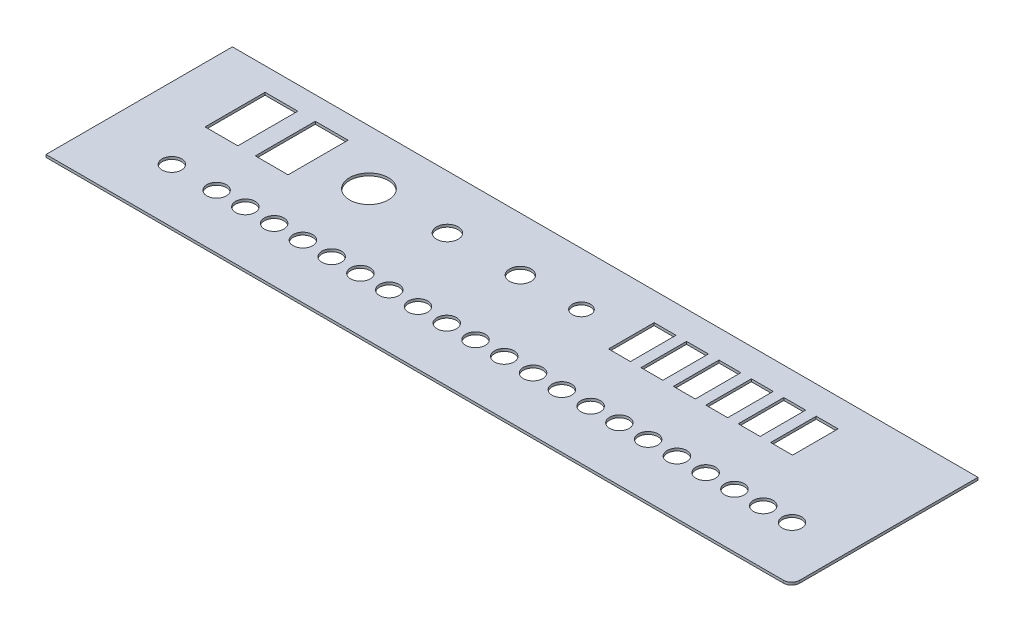
SolidWorks part; units mm, degrees
ref_plane "Front Plane" through (0, 0, 0) normal (0, 0, 1) x (1, 0, 0)
ref_plane "Top Plane" through (0, 0, 0) normal (0, 1, 0) x (1, 0, 0)
ref_plane "Right Plane" through (0, 0, 0) normal (1, 0, 0) x (0, 0, -1)
sketch "Boceto" plane through (0, 0, 0) normal (0, 1, 0) x (1, 0, 0)
  line L0 (-59.1, 30.6902) -> (-173.0029, 30.6902) construction
  line L5 (-59.1, -51.6098) -> (395.9, -51.6098) construction
  line L6 (-59.1, -51.6098) -> (-59.1, 63.3902) construction
  line L7 (-59.1, 63.3902) -> (395.9, 63.3902) construction
  line L8 (395.9, -51.6098) -> (395.9, 63.3902) construction
  line L9 (-28.6, 48.9902) -> (-8.6, 48.9902) construction
  line L10 (-28.6, 48.9902) -> (-28.6, 12.3902) construction
  line L11 (-28.6, 12.3902) -> (-8.6, 12.3902) construction
  line L12 (-8.6, 48.9902) -> (-8.6, 12.3902) construction
  line L13 (-28.6, 48.9902) -> (-8.6, 12.3902) construction
  line L14 (-28.6, 12.3902) -> (-8.6, 48.9902) construction
  line L15 (-59.1, -18.1098) -> (395.9, -18.1098) construction
  line L16 (2.4, 12.3902) -> (22.4, 12.3902) construction
  line L17 (2.4, 12.3902) -> (2.4, 48.9902) construction
  line L18 (2.4, 48.9902) -> (22.4, 48.9902) construction
  line L19 (22.4, 12.3902) -> (22.4, 48.9902) construction
  line L20 (2.4, 12.3902) -> (22.4, 48.9902) construction
  line L21 (2.4, 48.9902) -> (22.4, 12.3902) construction
  line L22 (174.9, 49.7902) -> (194.9, 49.7902) construction
  line L23 (174.9, 49.7902) -> (174.9, 11.7902) construction
  line L24 (174.9, 11.7902) -> (194.9, 11.7902) construction
  line L25 (194.9, 49.7902) -> (194.9, 11.7902) construction
  line L26 (174.9, 49.7902) -> (194.9, 11.7902) construction
  line L27 (174.9, 11.7902) -> (194.9, 49.7902) construction
  line L34 (211.4, 17.5561) -> (331, 17.5561) construction
  line L35 (211.4, 17.5561) -> (211.4, 46.5902) construction
  line L36 (211.4, 46.5902) -> (331, 46.5902) construction
  line L37 (331, 17.5561) -> (331, 46.5902) construction
  line L38 (211.4, 17.5561) -> (331, 46.5902) construction
  line L39 (211.4, 46.5902) -> (331, 17.5561) construction
  circle A0 centre (54.9, 29.6902) radius 11.1 construction
  circle A1 centre (102.75, 30.2402) radius 4.85 construction
  circle A2 centre (147.75, 30.2402) radius 4.85 construction
  circle A3 centre (-18.9, -18.1098) radius 6 construction
  circle A4 centre (8.7, -18.1098) radius 6 construction
  circle A5 centre (26.45, -18.1098) radius 6 construction
  circle A6 centre (44.2, -18.1098) radius 6 construction
  circle A7 centre (61.95, -18.1098) radius 6 construction
  circle A8 centre (79.7, -18.1098) radius 6 construction
  circle A9 centre (97.45, -18.1098) radius 6 construction
  circle A10 centre (115.2, -18.1098) radius 6 construction
  circle A11 centre (132.95, -18.1098) radius 6 construction
  circle A12 centre (150.7, -18.1098) radius 6 construction
  circle A13 centre (168.45, -18.1098) radius 6 construction
  circle A14 centre (186.2, -18.1098) radius 6 construction
  circle A15 centre (203.95, -18.1098) radius 6 construction
  circle A16 centre (221.7, -18.1098) radius 6 construction
  circle A17 centre (239.45, -18.1098) radius 6 construction
  circle A18 centre (257.2, -18.1098) radius 6 construction
  circle A19 centre (274.95, -18.1098) radius 6 construction
  circle A20 centre (292.7, -18.1098) radius 6 construction
  circle A21 centre (310.45, -18.1098) radius 6 construction
  circle A22 centre (328.2, -18.1098) radius 6 construction
  circle A23 centre (345.95, -18.1098) radius 6 construction
  circle A24 centre (363.7, -18.1098) radius 6 construction
  point P0 (0, 0)
  point P6 (-18.6, 30.6902)
  point P13 (12.4, 30.6902)
  point P24 (184.9, 30.7902)
  point P34 (271.2, 32.0731)
  dimension "D10" = 22.2
  dimension "D11" = 33.7
  dimension "D14" = 9.7
  dimension "D17" = 9.7
  dimension "D23" = 12
  dimension "D29" = 81.5
  dimension "D30" = 12
  dimension "D1" = 455
  dimension "D2" = 115
  dimension "D3" = 14.4
  dimension "D4" = 30.5
  dimension "D5" = 20
  dimension "D6" = 36.6
  dimension "D7" = 11
  dimension "D8" = 20
  dimension "D9" = 36.6
  dimension "D12" = 114
  dimension "D13" = 161.85
  dimension "D15" = 33.15
  dimension "D16" = 33.15
  dimension "D18" = 206.85
  dimension "D19" = 20
  dimension "D20" = 38
  dimension "D21" = 13.6
  dimension "D22" = 234
  dimension "D24" = 270.5
  dimension "D25" = 119.6
  dimension "D26" = 16.8
  dimension "D27" = 29.0341
  dimension "D28" = 40.2
  dimension "D31" = 27.6
  dimension "D32" = 21
sketch "Sketch4" plane through (0, 0, 0) normal (0, 1, 0) x (1, 0, 0)
  line L0 (-28.6, 48.9902) -> (-8.6, 12.3902) construction
  line L1 (-60.5474, 63.3902) -> (394.4526, 63.3902)
  line L3 (-60.5474, -51.6098) -> (391.9526, -51.6098)
  line L5 (-28.7093, 12.1902) -> (-8.4907, 12.1902)
  line L6 (-28.7093, 12.1902) -> (-28.7093, 49.1902)
  line L7 (-28.7093, 49.1902) -> (-8.4907, 49.1902)
  line L8 (-8.4907, 12.1902) -> (-8.4907, 49.1902)
  line L9 (-28.7093, 12.1902) -> (-8.4907, 49.1902) construction
  line L10 (-28.7093, 49.1902) -> (-8.4907, 12.1902) construction
  line L11 (-28.6, 12.3902) -> (-8.6, 48.9902) construction
  line L12 (2.4, 12.3902) -> (22.4, 48.9902) construction
  line L17 (2.2907, 12.1902) -> (2.2907, 49.1902)
  line L18 (2.2907, 12.1902) -> (22.5093, 12.1902)
  line L19 (22.5093, 12.1902) -> (22.5093, 49.1902)
  line L20 (2.2907, 49.1902) -> (22.5093, 49.1902)
  line L21 (102.75, 30.2402) -> (199.8359, 30.2402) construction
  line L22 (211.4, 32.0731) -> (331, 32.0731) construction
  line L23 (211.4, 17.5561) -> (211.4, 46.5902) construction
  line L24 (331, 17.5561) -> (331, 46.5902) construction
  line L25 (247.9, 46.1231) -> (247.9, 18.0231)
  line L26 (227.9, 46.1231) -> (214.4, 46.1231)
  line L27 (227.9, 46.1231) -> (227.9, 18.0231)
  line L28 (227.9, 18.0231) -> (214.4, 18.0231)
  line L29 (214.4, 46.1231) -> (214.4, 18.0231)
  line L30 (227.9, 46.1231) -> (214.4, 18.0231) construction
  line L31 (227.9, 18.0231) -> (214.4, 46.1231) construction
  line L32 (247.9, 46.1231) -> (234.4, 46.1231)
  line L33 (234.4, 46.1231) -> (234.4, 18.0231)
  line L34 (247.9, 18.0231) -> (234.4, 18.0231)
  line L35 (267.9, 46.1231) -> (267.9, 18.0231)
  line L36 (267.9, 46.1231) -> (254.4, 46.1231)
  line L37 (254.4, 46.1231) -> (254.4, 18.0231)
  line L38 (267.9, 18.0231) -> (254.4, 18.0231)
  line L39 (287.9, 46.1231) -> (287.9, 18.0231)
  line L40 (287.9, 46.1231) -> (274.4, 46.1231)
  line L41 (274.4, 46.1231) -> (274.4, 18.0231)
  line L42 (287.9, 18.0231) -> (274.4, 18.0231)
  line L43 (307.9, 46.1231) -> (307.9, 18.0231)
  line L44 (307.9, 46.1231) -> (294.4, 46.1231)
  line L45 (294.4, 46.1231) -> (294.4, 18.0231)
  line L46 (307.9, 18.0231) -> (294.4, 18.0231)
  line L47 (327.9, 46.1231) -> (327.9, 18.0231)
  line L48 (327.9, 46.1231) -> (314.4, 46.1231)
  line L49 (314.4, 46.1231) -> (314.4, 18.0231)
  line L50 (327.9, 18.0231) -> (314.4, 18.0231)
  line L52 (-60.5474, 63.3902) -> (-63.0474, 63.3902)
  line L54 (-60.5474, -51.6098) -> (-63.0474, -51.6098)
  line L55 (-63.0474, 63.3902) -> (-63.0474, -51.6098)
  line L58 (394.4526, 63.3902) -> (396.9526, 63.3902)
  line L59 (396.9526, -46.6098) -> (396.9526, 63.3902)
  circle A0 centre (54.9, 29.6902) radius 11.95
  circle A1 centre (102.75, 30.2402) radius 6.65
  circle A4 centre (147.75, 30.2402) radius 6.65
  circle A6 centre (184.9, 30.7902) radius 5.6
  circle A7 centre (-18.9, -18.1098) radius 6
  circle A8 centre (8.7, -18.1098) radius 6
  circle A9 centre (26.45, -18.1098) radius 6
  circle A10 centre (44.2, -18.1098) radius 6
  circle A11 centre (61.95, -18.1098) radius 6
  circle A12 centre (79.7, -18.1098) radius 6
  circle A13 centre (97.45, -18.1098) radius 6
  circle A14 centre (115.2, -18.1098) radius 6
  circle A15 centre (132.95, -18.1098) radius 6
  circle A16 centre (150.7, -18.1098) radius 6
  circle A17 centre (168.45, -18.1098) radius 6
  circle A18 centre (186.2, -18.1098) radius 6
  circle A19 centre (203.95, -18.1098) radius 6
  circle A20 centre (221.7, -18.1098) radius 6
  circle A21 centre (239.45, -18.1098) radius 6
  circle A22 centre (257.2, -18.1098) radius 6
  circle A23 centre (274.95, -18.1098) radius 6
  circle A24 centre (292.7, -18.1098) radius 6
  circle A25 centre (310.45, -18.1098) radius 6
  circle A26 centre (328.2, -18.1098) radius 6
  circle A27 centre (345.95, -18.1098) radius 6
  circle A28 centre (363.7, -18.1098) radius 6
  arc A29 (396.9526, -46.6098) -> (391.9526, -51.6098) centre (391.9526, -46.6098) cw
  point P6 (-18.6, 30.6902)
  point P15 (12.4, 30.6902)
  point P40 (221.15, 32.0731)
  dimension "D3" = 23.9
  dimension "D4" = 13.3
  dimension "D5" = 2
  dimension "D6" = 11.2
  dimension "D11" = 12
  dimension "D13" = 5
  dimension "D1" = 37
  dimension "D2" = 2
  dimension "D7" = 13.5
  dimension "D8" = 28.1
  dimension "D9" = 3
  dimension "D14" = 2.5
  dimension "D15" = 2.5
  dimension "D10" = 6
  dimension "D12" = 21
extrude "Boss-Extrude1" add sketch "Sketch4" along normal blind 1.6
